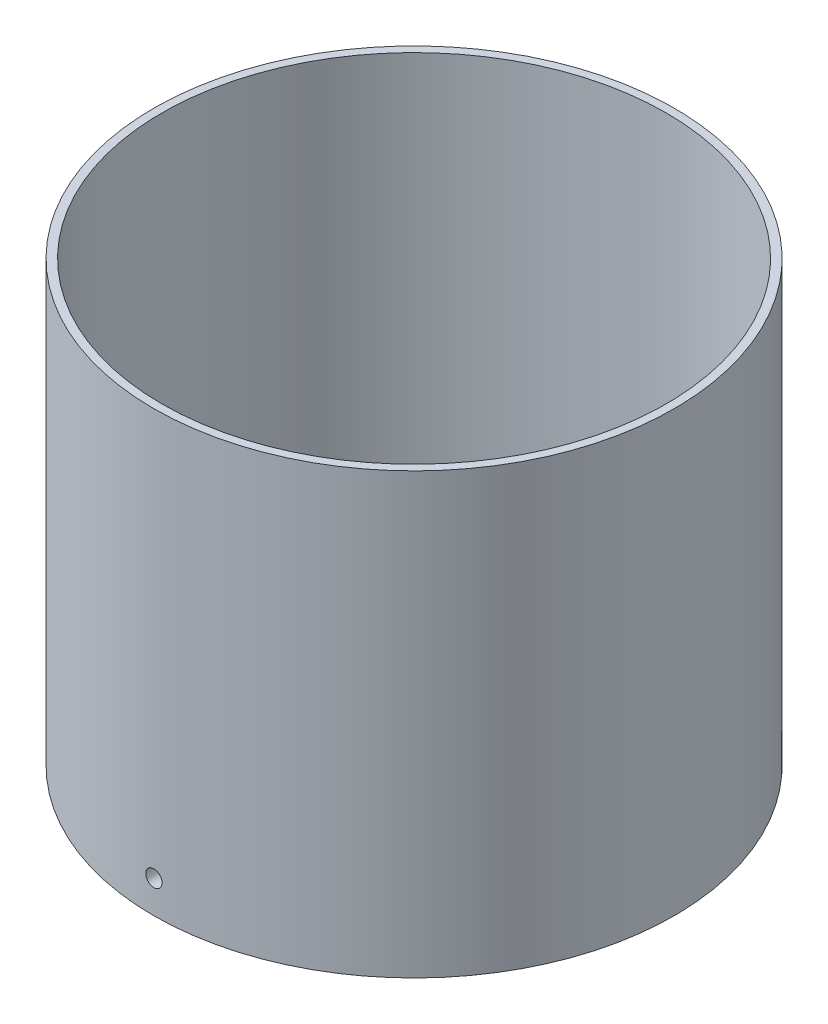
SolidWorks part; units mm, degrees
ref_plane "Front Plane" through (0, 0, 0) normal (0, 0, 1) x (1, 0, 0)
ref_plane "Top Plane" through (0, 0, 0) normal (0, 1, 0) x (1, 0, 0)
ref_plane "Right Plane" through (0, 0, 0) normal (1, 0, 0) x (0, 0, -1)
sketch "Sketch1" plane through (0, 0, 0) normal (0, 1, 0) x (1, 0, 0)
  circle A0 centre (0, 0) radius 101.6
  circle A1 centre (0, 0) radius 95.25
  dimension "D1" = 203.2
  dimension "D2" = 190.5
extrude "Boss-Extrude1" add sketch "Sketch1" along normal blind 25.4
sketch "Sketch2" plane through (0, 0, 0) normal (0, 0, 1) x (1, 0, 0)
  circle A0 centre (0, 12.7) radius 3.175
  dimension "D1" = 6.35
extrude "Cut-Extrude1" cut sketch "Sketch2" against normal through all and the other way through all
sketch "Sketch3" plane through (0, 0, 0) normal (1, 0, 0) x (0, 0, -1)
  circle A0 centre (0, 12.7) radius 1.5875
  dimension "D1" = 3.175
extrude "Cut-Extrude3" [suppressed] cut sketch "Sketch3" against normal through all
sketch "Sketch4" plane through (0, 0, 0) normal (1, 0, 0) x (0, 0, -1)
  line L0 (0, 0) -> (0, 72.5565) construction
pattern_circular "CirPattern1" [suppressed] count 24 over 360 about axis through (0, 0, 0) along (0, 1, 0) reverse direction yes of bodies 103
sketch "Sketch5" plane through (0, 25.4, 0) normal (0, 1, 0) x (1, 0, 0)
  circle A0 centre (0, 0) radius 98.425
  circle A1 centre (0, 0) radius 101.6
extrude "Boss-Extrude2" add sketch "Sketch5" along normal blind 146.05
sketch "Sketch6" plane through (0, 0, 0) normal (0, -1, 0) x (1, 0, 0)
  circle A0 centre (0, 0) radius 101.6
  circle A1 centre (0, 0) radius 98.425
extrude "Boss-Extrude3" [suppressed] add sketch "Sketch6" along normal blind 133.35
